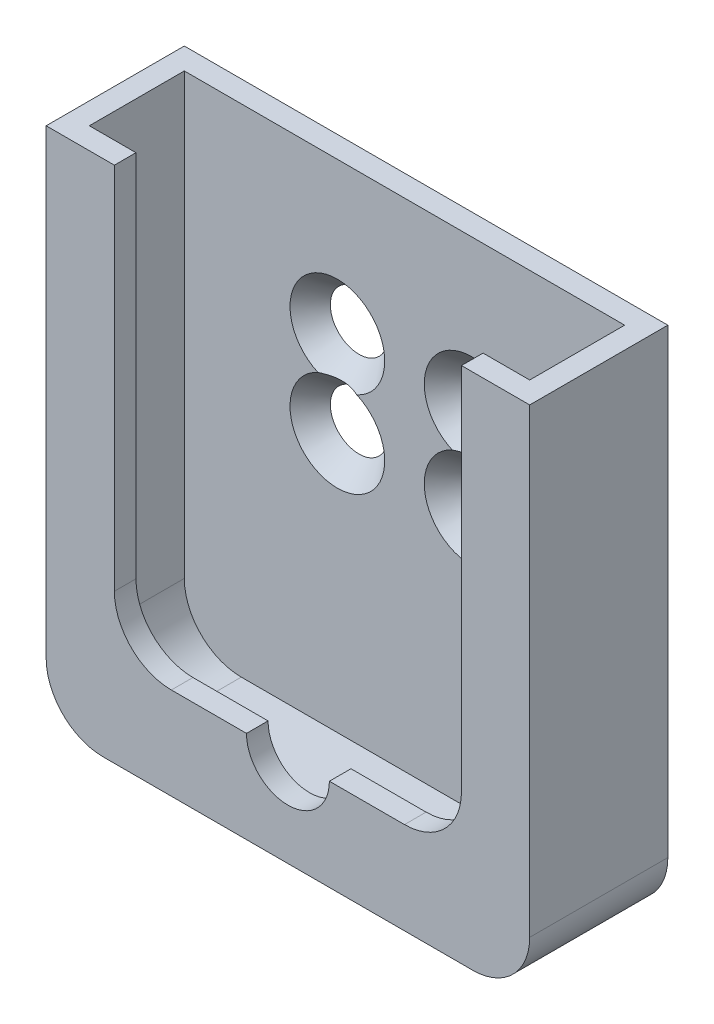
SolidWorks part; units mm, degrees
ref_plane "Front Plane" through (0, 0, 0) normal (0, 0, 1) x (1, 0, 0)
ref_plane "Top Plane" through (0, 0, 0) normal (0, 1, 0) x (1, 0, 0)
ref_plane "Right Plane" through (0, 0, 0) normal (1, 0, 0) x (0, 0, -1)
sketch "Sketch1" plane through (0, 0, 0) normal (0, 0, 1) x (1, 0, 0)
  line L1 (0, 0) -> (71.12, 0)
  line L2 (0, 0) -> (0, 76.2)
  line L3 (0, 76.2) -> (71.12, 76.2)
  line L4 (71.12, 0) -> (71.12, 76.2)
  dimension "D1" = 71.12
  dimension "D2" = 76.2
extrude "Boss-Extrude1" add sketch "Sketch1" along normal mid plane 20.32
sketch "Sketch2" plane through (0, 76.2, 0) normal (0, 1, 0) x (1, 0, 0)
  line L0 (3.175, 6.985) -> (67.945, 6.985)
  line L1 (67.945, 6.985) -> (67.945, -6.985)
  line L2 (3.175, -6.985) -> (67.945, -6.985)
  line L3 (71.12, -10.16) -> (0, -10.16) construction
  line L8 (3.175, -6.985) -> (3.175, 6.985)
  line L9 (71.12, 10.16) -> (0, 10.16) construction
  line L10 (0, -10.16) -> (0, 10.16) construction
  line L11 (71.12, -10.16) -> (71.12, 10.16) construction
  line L12 (35.56, 16.362) -> (35.56, -10.4064) construction
  point P17 (35.56, 6.985)
  dimension "D1" = 3.175
  dimension "D2" = 3.175
  dimension "D3" = 3.175
  dimension "D4" = 3.175
extrude "Cut-Extrude1" cut sketch "Sketch2" against normal offset from surface (73.025 mm away) 3.175 up to face at (35.56, 0, 0)
sketch "Sketch3" plane through (0, 76.2, 0) normal (0, 1, 0) x (1, 0, 0)
  line L0 (71.12, -10.16) -> (0, -10.16) construction
  line L1 (10.033, -10.16) -> (61.087, -10.16)
  line L2 (10.033, -10.16) -> (10.033, -6.985)
  line L3 (10.033, -6.985) -> (61.087, -6.985)
  line L4 (61.087, -10.16) -> (61.087, -6.985)
  line L5 (3.175, -6.985) -> (67.945, -6.985) construction
  line L6 (35.56, 12.6207) -> (35.56, -18.9707) construction
  line L7 (71.12, 10.16) -> (0, 10.16) construction
  point P13 (35.56, 10.16)
  dimension "D1" = 51.054
extrude "Cut-Extrude2" cut sketch "Sketch3" against normal offset from surface (62.6618 mm away) 13.5382 up to face at (35.56, 0, 0)
fillet "Fillet1" radius 8.382 4 edges at (67.945, 3.175, 0) (3.175, 3.175, 0) (10.033, 13.5382, 8.5725) (61.087, 13.5382, 8.5725)
fillet "Fillet2" radius 8.382 2 edges at (0, 0, 0) (71.12, 0, 0)
sketch "Sketch4" plane through (0, 0, 10.16) normal (0, 0, 1) x (1, 0, 0)
  line L0 (52.705, 13.5382) -> (18.415, 13.5382) construction
  circle A0 centre (35.56, 13.5382) radius 6.096
  dimension "D1" = 12.192
extrude "Cut-Extrude3" cut sketch "Sketch4" against normal up to next
hole_wizard "CSK for 1/4 Flat Head Socket Cap Screw1" positions "Sketch8" profile "Sketch9" countersink size "1/4" standard "ANSI Inch" end condition through all
sketch "Sketch8" plane through (0, 0, -6.985) normal (0, 0, 1) x (1, 0, 0)
  line L1 (35.56, 76.2) -> (35.56, 28.3115) construction
  line L3 (67.945, 76.2) -> (3.175, 76.2) construction
  line L4 (11.557, 3.175) -> (59.563, 3.175) construction
  point P0 (25.6871, 53.975)
  point P2 (45.4329, 53.975)
  point P4 (45.4329, 41.275)
  point P6 (25.6871, 41.275)
  point P20 (35.56, 76.2)
  dimension "D1" = 19.7459
  dimension "D2" = 12.7
  dimension "D3" = 38.1
sketch "Sketch9" plane through (25.6871, 53.975, -6.985) normal (1, 0, 0) x (0, -1, 0)
  line L0 (0, 0) -> (0, 3.175)
  line L1 (0, 3.175) -> (3.3782, 3.175)
  line L2 (3.3782, 3.175) -> (3.3782, 4.1256)
  line L3 (3.3782, 4.1256) -> (6.9645, 0)
  line L5 (6.9645, 0) -> (0, 0)
  line L6 (-3.3782, 4.1256) -> (-6.9645, 0) construction
  line L11 (0, -6.35) -> (0, 107.95) construction
  dimension "Thru Hole Dia." = 6.7564
  dimension "Thru Hole Depth" = 3.175
  dimension "Near C'Sink Dia." = 13.929
  dimension "Near C'Sink Angle" = 82
equation "\"width\"= 2.53in'Phone width"
equation "\"D1@Sketch1\" = \"width\" + 2 * \"wall\" +2*\"margin\"'Overall width of holster"
equation "\"wall\"= 0.125in'Metal thickness"
equation "\"height\"= 3in'Overall holster height"
equation "\"D2@Sketch1\"= \"height\"'Overall holster height"
equation "\"depth\"= 0.53in'Thickness of phone"
equation "\"D1@Boss-Extrude1\"= \"depth\" + 2 * \"wall\" + 2*\"margin\" 'Overal depth of holster"
equation "\"D3@Sketch2\"=\"wall\""
equation "\"D4@Sketch2\"= \"wall\""
equation "\"screen_width\"= 2.01in'Width of visible screen"
equation "\"margin\"= 0.01in'Slop to allow the phone to fit properly"
equation "\"D2@Sketch2\" = \"wall\""
equation "\"D1@Sketch2\"=\"wall\""
equation "\"D1@Cut-Extrude1\"=\"wall\""
equation "\"D1@Sketch3\"=\"screen_width\""
equation "\"D1@Cut-Extrude2\" = \"lower_edge\" + \"wall\""
equation "\"lower_edge\"= .408'How deep the phone sits in the holster"
equation "\"tool_diam\"= .66'Diameter of the tool used for undercuts, set to match the corners of the phone"
equation "\"D1@Fillet1\"=\"tool_diam\"/2"
equation "\"D1@Fillet2\"=\"tool_diam\"/2"
equation "\"button_cutout\"= .48in'Cutout for the iPhone button"
equation "\"D1@Sketch4\" = \"button_cutout\""
